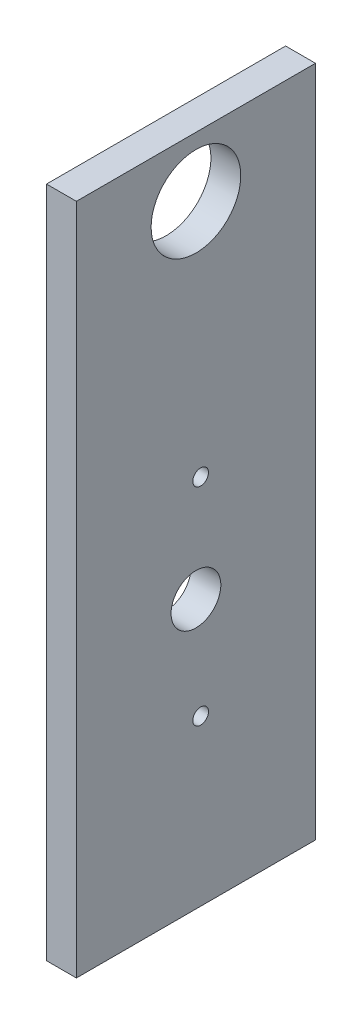
SolidWorks part; units mm, degrees
ref_plane "Front Plane" through (0, 0, 0) normal (0, 0, 1) x (1, 0, 0)
ref_plane "Top Plane" through (0, 0, 0) normal (0, 1, 0) x (1, 0, 0)
ref_plane "Right Plane" through (0, 0, 0) normal (1, 0, 0) x (0, 0, -1)
sketch "Sketch1" plane through (0, 0, 0) normal (0, 1, 0) x (1, 0, 0)
  line L1 (-4.7625, 38.1) -> (4.7625, 38.1)
  line L2 (-4.7625, 38.1) -> (-4.7625, -38.1)
  line L3 (-4.7625, -38.1) -> (4.7625, -38.1)
  line L4 (4.7625, 38.1) -> (4.7625, -38.1)
  line L5 (-4.7625, 38.1) -> (4.7625, -38.1) construction
  line L6 (-4.7625, -38.1) -> (4.7625, 38.1) construction
  point P0 (0, 0)
  dimension "D1" = 76.2
  dimension "D2" = 9.525
extrude "Boss-Extrude1" add sketch "Sketch1" along normal mid plane 214.376
sketch "Sketch3" plane through (-4.7625, 0, 0) normal (-1, 0, 0) x (0, 0, 1)
  line L2 (-38.1, 107.188) -> (38.1, 107.188) construction
  circle A0 centre (0, 88.138) radius 14.2875
  point P12 (-38.1, 107.188)
  dimension "D1" = 28.575
  dimension "D2" = 19.05
extrude "Cut-Extrude2" cut sketch "Sketch3" against normal blind 45.974
fillet "Fillet1" [suppressed] radius 25.4
sketch "Sketch4" plane through (-4.7625, 0, 0) normal (-1, 0, 0) x (0, 0, 1)
  line L0 (-38.1, 107.188) -> (-38.1, -107.188) construction
  circle A0 centre (-1.5, 11.3124) radius 2.5
  circle A1 centre (-1.5, -54.6876) radius 2.5
  circle A2 centre (0, -21.6876) radius 7.9248
  dimension "D4" = 36.6
  dimension "D5" = 5
  dimension "D2" = 15.8496
  dimension "D1" = 66
  dimension "D3" = 33
  dimension "D6" = 1.5
  dimension "D7" = 1.5
  dimension "D8" = 38.1
extrude "Cut-Extrude3" cut sketch "Sketch4" against normal through all
